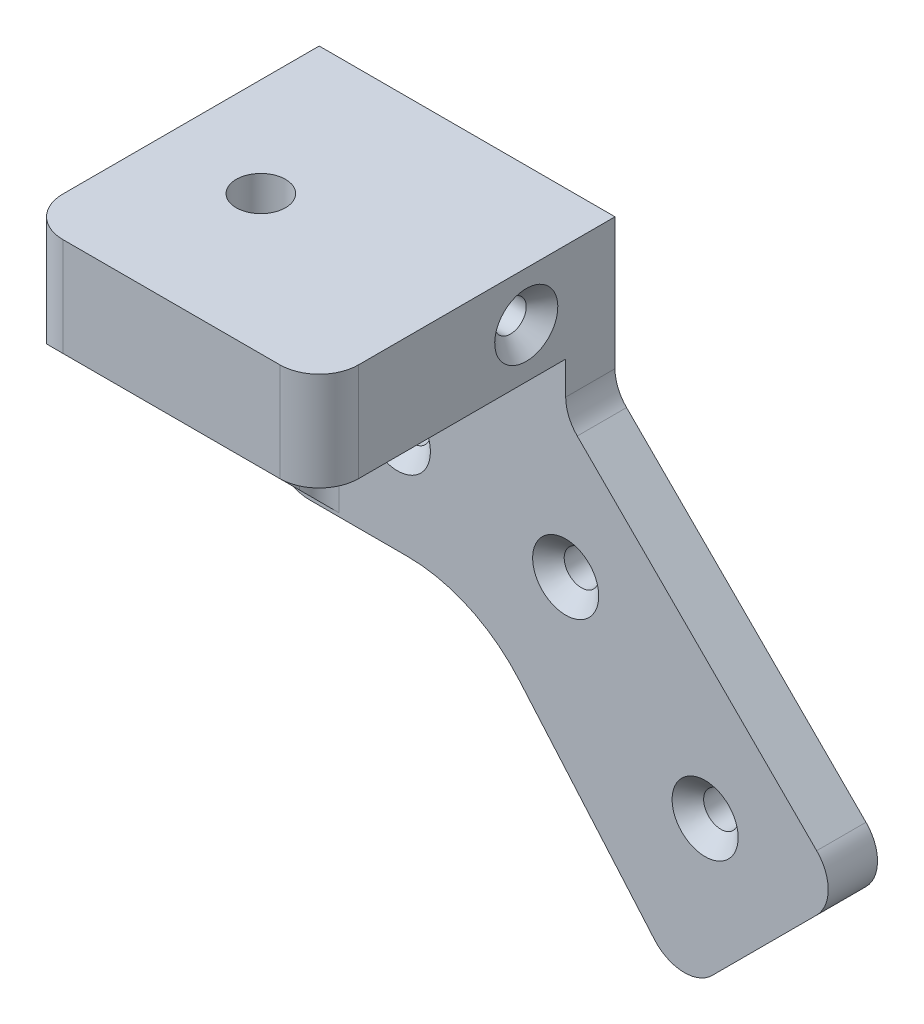
SolidWorks part; units mm, degrees
ref_plane "Front Plane" through (0, 0, 0) normal (0, 0, 1) x (1, 0, 0)
ref_plane "Top Plane" through (0, 0, 0) normal (0, 1, 0) x (1, 0, 0)
ref_plane "Right Plane" through (0, 0, 0) normal (1, 0, 0) x (0, 0, -1)
sketch "Sketch1" plane through (0, 0, 0) normal (0, 0, 1) x (1, 0, 0)
  line L0 (15, 27.5) -> (15, 12.5)
  line L5 (-15, 27.5) -> (15, 27.5)
  line L6 (-15, 27.5) -> (-15, -27.5)
  line L7 (-15, -27.5) -> (15, -27.5)
  line L9 (15, 12.5) -> (43.2843, -15.7843)
  line L10 (-15, -27.5) -> (15, 27.5) construction
  line L11 (43.2843, -15.7843) -> (23.2843, -35.7843)
  line L12 (23.2843, -35.7843) -> (15, -27.5)
  point P0 (0, 0)
  dimension "D1" = 45
  dimension "D2" = 55
  dimension "D3" = 30
  dimension "D4" = 40
  dimension "D5" = 15
extrude "Boss-Extrude1" add sketch "Sketch1" along normal blind 5
sketch "Sketch3" plane through (0, 0, 5) normal (0, 0, 1) x (1, 0, 0)
  line L0 (15, 12.5) -> (15, 27.5) construction
  line L1 (-15, 27.5) -> (15, 27.5)
  line L2 (-15, 27.5) -> (-15, 17.5)
  line L3 (-15, 17.5) -> (15, 17.5)
  line L4 (15, 27.5) -> (15, 17.5)
  dimension "D1" = 10
extrude "Boss-Extrude2" add sketch "Sketch3" along normal blind 25
sketch "Sketch4" plane through (0, 27.5, 0) normal (0, 1, 0) x (1, 0, 0)
  line L0 (-15, -30) -> (-15, 0) construction
  line L1 (15, -30) -> (-15, -30) construction
  line L2 (15, -30) -> (15, -5) construction
  line L3 (15, -5) -> (-15, -5) construction
  line L4 (-15, -30) -> (-15, -5) construction
  line L5 (15, -30) -> (15, 0) construction
  line L6 (-15, 0) -> (15, 0) construction
  line L7 (-15, 0) -> (-15, 5) construction
  line L8 (-15, 5) -> (15, 5) construction
  line L9 (15, 0) -> (15, 5) construction
  line L10 (15, -22.575) -> (-15, -22.575) construction
  circle A0 centre (-5, -15.9175) radius 2.5
  circle A1 centre (-5, -15.9175) radius 6.6575 construction
  circle A2 centre (-5, -16.15) radius 6.425 construction
  point P19 (-11.6532, -25.3122)
  point P22 (15, -22.575)
  point P23 (-15, -22.575)
  dimension "D3" = 13.315
  dimension "D4" = 5
  dimension "D7" = 21.15
  dimension "D8" = 12.85
  dimension "D1" = 25
  dimension "D2" = 5
  dimension "D6" = 20
extrude "Cut-Extrude1" cut sketch "Sketch4" against normal through all
sketch "Sketch6" plane through (-15, 0, 0) normal (-1, 0, 0) x (0, 0, 1)
  line L0 (30, 17.5) -> (5, -7.5)
  line L1 (5, 17.5) -> (5, -27.5) construction
  dimension "D1" = 45
rib "Rib1" sketch "Sketch6" sketch "Sketch6" thickness 5 extrusion direction parallel to sketch draft on no parameters "D1"=5
sketch "Sketch7" plane through (0, 0, 5) normal (0, 0, 1) x (1, 0, 0)
  line L0 (10.2934, -13.0651) -> (26.8198, -32.2487)
  line L1 (-15, -7.8553) -> (-1.0711, -7.8553)
  line L2 (-15, -7.8553) -> (-15, -27.5)
  line L3 (-15, -7.5) -> (-15, -27.5) construction
  line L4 (-15, -27.5) -> (15, -27.5) construction
  line L5 (15, 27.5) -> (-15, 27.5) construction
  line L6 (23.2843, -35.7843) -> (43.2843, -15.7843) construction
  line L7 (-15, -27.5) -> (23.2843, -35.7843)
  line L8 (23.2843, -35.7843) -> (26.8198, -32.2487)
  arc A0 (10.2934, -13.0651) -> (-1.0711, -7.8553) centre (-1.0711, -22.8553) ccw
  circle A1 centre (-1.0711, -22.8553) radius 14 construction
  dimension "D1" = 1
  dimension "D2" = 5
extrude "Cut-Extrude2" cut sketch "Sketch7" against normal up to vertex (5 mm away) up to point (-15, -27.5, 0)
sketch "Sketch8" plane through (0, 17.5, 0) normal (0, -1, 0) x (-1, 0, 0)
  line L1 (0.2657, -15.9175) -> (2.6329, -20.0175)
  line L2 (2.6329, -20.0175) -> (7.3671, -20.0175)
  line L3 (7.3671, -20.0175) -> (9.7343, -15.9175)
  line L4 (9.7343, -15.9175) -> (7.3671, -11.8175)
  line L5 (7.3671, -11.8175) -> (2.6329, -11.8175)
  line L6 (2.6329, -11.8175) -> (0.2657, -15.9175)
  circle A0 centre (5, -15.9175) radius 4.1 construction
  dimension "D1" = 8.2
extrude "Cut-Extrude3" cut sketch "Sketch8" against normal blind 5
fillet "Fillet1" radius 4 2 edges at (-15, 22.5, 30) (15, 22.5, 30)
sketch "Sketch9" plane through (0, 0, 5) normal (0, 0, 1) x (1, 0, 0)
  line L0 (15, -1.6421) -> (22.0711, 5.4289) construction
  line L1 (43.2843, -15.7843) -> (15, 12.5) construction
  line L2 (29.1421, -15.7843) -> (36.2132, -8.7132) construction
  line L3 (26.8198, -32.2487) -> (43.2843, -15.7843) construction
  line L4 (15, 12.5) -> (-5.3553, -7.8553) construction
  line L5 (-1.0711, -7.8553) -> (-15, -7.8553) construction
  line L6 (15, 12.5) -> (-15, 12.5) construction
  line L7 (-15, 13.5) -> (-15, -7.5) construction
  circle A0 centre (15, -1.6421) radius 1.75
  circle A1 centre (29.1421, -15.7843) radius 1.75
  circle A2 centre (-2.0711, 2.5) radius 1.75
  dimension "D1" = 3.5
  dimension "D5" = 5
  dimension "D2" = 10
  dimension "D3" = 10
  dimension "D4" = 20
  dimension "D6" = 10
extrude "Cut-Extrude4" cut sketch "Sketch9" against normal through all
chamfer "Chamfer1" distance 1.6 angle 45 3 edges at (30.8921, -15.7843, 5) (16.75, -1.6421, 5) (-0.3211, 2.5, 5)
fillet "Fillet2" radius 4 4 edges at (15, 12.5, 2.5) (43.2843, -15.7843, 2.5) (26.8198, -32.2487, 2.5) (-15, -7.8553, 2.5)
sketch "Sketch10" plane through (15, 0, 0) normal (1, 0, 0) x (0, 0, -1)
  line L0 (-9, 17.5) -> (-9, 27.5) construction
  line L1 (-26, 17.5) -> (-5, 17.5) construction
  line L2 (-26, 27.5) -> (0, 27.5) construction
  line L3 (0, 14.1569) -> (0, 27.5) construction
  circle A0 centre (-9, 22.5) radius 1.6
  dimension "D1" = 3.2
  dimension "D2" = 9
extrude "Cut-Extrude5" cut sketch "Sketch10" against normal through all
sketch "Sketch11" plane through (-15, 0, 0) normal (-1, 0, 0) x (0, 0, 1)
  line L1 (10.5877, 19.75) -> (12.1754, 22.5)
  line L2 (12.1754, 22.5) -> (10.5877, 25.25)
  line L3 (10.5877, 25.25) -> (7.4123, 25.25)
  line L4 (7.4123, 25.25) -> (5.8246, 22.5)
  line L5 (5.8246, 22.5) -> (7.4123, 19.75)
  line L6 (7.4123, 19.75) -> (10.5877, 19.75)
  circle A0 centre (9, 22.5) radius 2.75 construction
  dimension "D1" = 5.5
extrude "Cut-Extrude6" cut sketch "Sketch11" against normal blind 4
chamfer "Chamfer2" distance 1.6 angle 45 1 edges at (15, 24.1, 9)
fillet "Fillet3" radius 2 1 edges at (-10, 5, 5)
